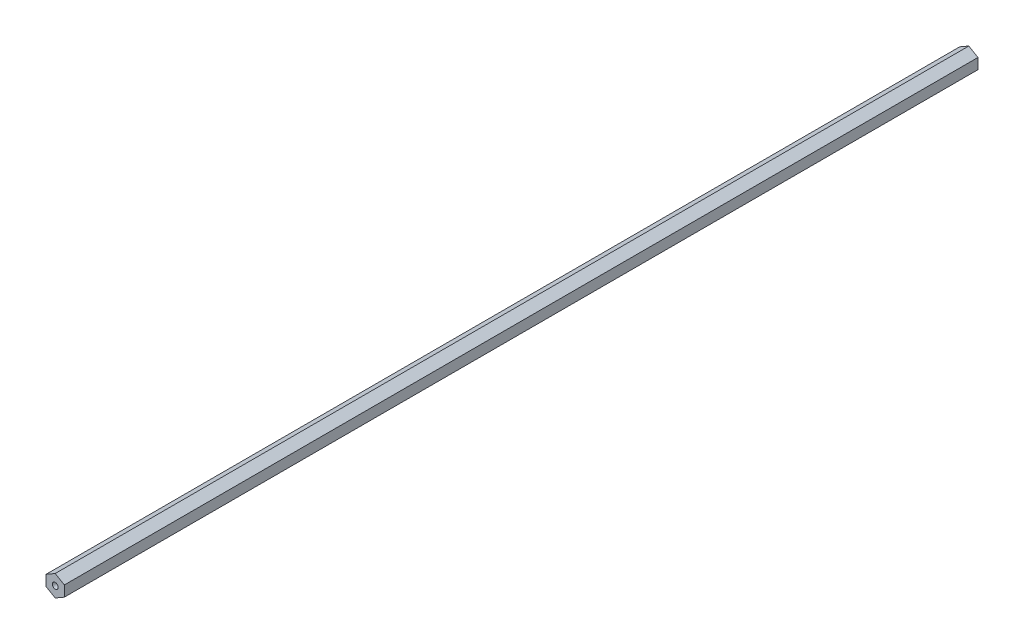
SolidWorks part; units mm, degrees
ref_plane "Front Plane" through (0, 0, 0) normal (0, 0, 1) x (1, 0, 0)
ref_plane "Top Plane" through (0, 0, 0) normal (0, 1, 0) x (1, 0, 0)
ref_plane "Right Plane" through (0, 0, 0) normal (1, 0, 0) x (0, 0, -1)
sketch "Sketch1" plane through (0, 0, 0) normal (0, 0, 1) x (1, 0, 0)
  line L1 (6.35, -3.6662) -> (6.35, 3.6662)
  line L2 (6.35, 3.6662) -> (0, 7.3323)
  line L3 (0, 7.3323) -> (-6.35, 3.6662)
  line L4 (-6.35, 3.6662) -> (-6.35, -3.6662)
  line L5 (-6.35, -3.6662) -> (0, -7.3323)
  line L6 (0, -7.3323) -> (6.35, -3.6662)
  circle A0 centre (0, 0) radius 6.35 construction
  dimension "D1" = 12.7
extrude "Boss-Extrude1" add sketch "Sketch1" along normal mid plane 632.023
sketch "Sketch2" plane through (0, 0, 316.0115) normal (0, 0, 1) x (1, 0, 0)
  circle A0 centre (0, 0) radius 2.4892
  dimension "D1" = 4.9784
hole_wizard "#10-32 Tapped Hole1" positions "3DSketch1" profile "Sketch3" tap size "#10-32" standard "ANSI Inch"
sketch3d "3DSketch1"
  line L1 (-6.35, 3.6662, -316.0115) -> (-6.35, -3.6662, -316.0115) construction
  point P0 (0, 0, 316.0115)
  point P3 (0, 0, -316.0115)
  point P13 (-6.35, 0, -316.0115)
sketch "Sketch3" plane through (0, 0, 316.0115) normal (1, 0, 0) x (0, -1, 0)
  line L0 (0, 0) -> (0, 17.5608)
  line L1 (0, 17.5608) -> (2.0193, 16.3474)
  line L2 (2.0193, 16.3474) -> (2.0193, 0)
  line L5 (2.0193, 0) -> (0, 0)
  line L10 (0, 17.5608) -> (-2.0193, 16.3474) construction
  line L11 (0, -6.35) -> (0, 107.95) construction
  dimension "Tap Drill Dia." = 4.0386
  dimension "Tap Drill Depth" = 16.3474
  dimension "Drill Angle" = 118
cosmetic thread "Hole Thread1"
cosmetic thread "Hole Thread2"
